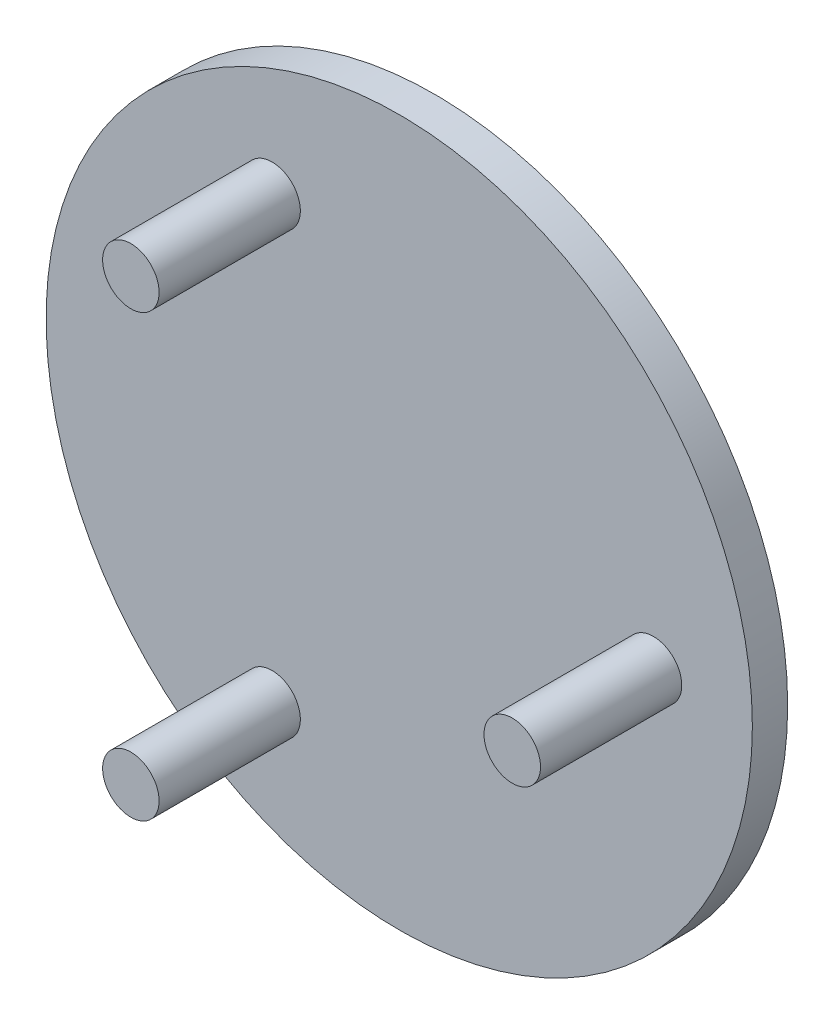
SolidWorks part; units mm, degrees
ref_plane "前视基准面" through (0, 0, 0) normal (0, 0, 1) x (1, 0, 0)
ref_plane "上视基准面" through (0, 0, 0) normal (0, 1, 0) x (1, 0, 0)
ref_plane "右视基准面" through (0, 0, 0) normal (1, 0, 0) x (0, 0, -1)
other "Configuration Table"
sketch "Sketch1" plane through (0, 0, 0) normal (0, 0, 1) x (1, 0, 0)
  circle A0 centre (0, 0) radius 50
extrude "Boss-Extrude1" add sketch "Sketch1" against normal blind 5
sketch "Sketch2" plane through (0, 0, 0) normal (0, 0, 1) x (1, 0, 0)
  circle A0 centre (36, 0) radius 4
  circle A1 centre (-18, 31.1769) radius 4
  circle A2 centre (-18, -31.1769) radius 4
extrude "Boss-Extrude2" add sketch "Sketch2" along normal blind 20
ref_plane "top_surface" through (0, 0, 0) normal (0, 0, 1) x (1, 0, 0)
sketch3d "3DSketch1"
  line L0 (0, 0, 0) -> (0, 0, 50) construction
ref_axis "main_axis" through (0, 0, 0) along (0, 0, 1)
sketch3d "3DSketch2"
  line L0 (36, 0, 0) -> (36, 0, 20) construction
ref_axis "pin_axis_1" through (36, 0, 0) along (0, 0, 1)
sketch3d "3DSketch3"
  line L0 (-18, 31.1769, 0) -> (-18, 31.1769, 20) construction
ref_axis "pin_axis_2" through (-18, 31.1769, 0) along (0, 0, 1)
sketch3d "3DSketch4"
  line L0 (-18, -31.1769, 0) -> (-18, -31.1769, 20) construction
ref_axis "pin_axis_3" through (-18, -31.1769, 0) along (0, 0, 1)
